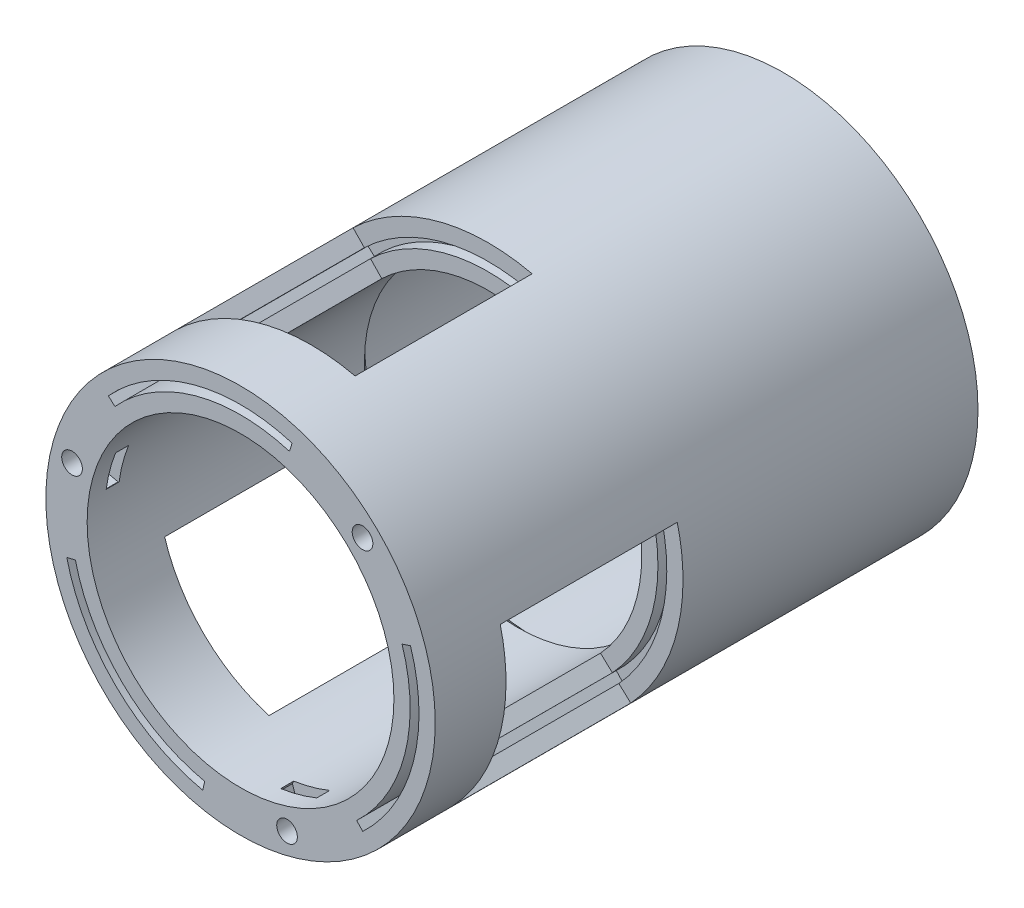
SolidWorks part; units mm, degrees
material "PEI"
ref_plane "Alzado" through (0, 0, 0) normal (0, 0, 1) x (1, 0, 0)
ref_plane "Planta" through (0, 0, 0) normal (0, 1, 0) x (1, 0, 0)
ref_plane "Vista lateral" through (0, 0, 0) normal (1, 0, 0) x (0, 0, -1)
sketch "Croquis1" plane through (0, 0, 0) normal (0, 0, 1) x (1, 0, 0)
  circle A0 centre (0, 0) radius 33
  circle A1 centre (0, 0) radius 29
  dimension "D1" = 66
  dimension "D2" = 4
extrude "Boss-Extrude1" add sketch "Croquis1" along normal blind 92
ref_axis "Eje1" through (0, 0, 92) along (0, 0, -1)
ref_plane "Plano corte lateral" through (0, 0, 0) normal (0.2419, -0.9703, 0) x (0, 0, -1)
sketch "Sketch8" plane through (0, 0, 0) normal (0, 0, -1) x (-1, 0, 0)
  arc A0 (-4, -28.7228) -> (4, -28.7228) centre (0, 0) ccw
  circle A1 centre (0, 0) radius 29 construction
  arc A2 (-4, -28.7228) -> (4, -28.7228) centre (0, -30.3008) cw
  arc A3 (-28.7228, 4) -> (-28.7228, -4) centre (0, 0) ccw
  arc A4 (-28.7228, 4) -> (-28.7228, -4) centre (-30.3008, 0) cw
  arc A5 (4, 28.7228) -> (-4, 28.7228) centre (0, 0) ccw
  arc A6 (4, 28.7228) -> (-4, 28.7228) centre (0, 30.3008) cw
  arc A7 (28.7228, -4) -> (28.7228, 4) centre (0, 0) ccw
  arc A8 (28.7228, -4) -> (28.7228, 4) centre (30.3008, 0) cw
  point P8 (0, -26.0008)
  point P20 (0, 0)
  dimension "D1" = 4.3
  dimension "D2" = 8
  dimension "D3" = 4
extrude "Boss-Extrude4" add sketch "Sketch8" against normal blind 15
sketch "Sketch9" plane through (0, 0, 0) normal (0, 0, -1) x (-1, 0, 0)
  circle A0 centre (0, -29) radius 1.75
  circle A1 centre (0, 0) radius 29 construction
  circle A2 centre (0, 0) radius 33 construction
  circle A3 centre (-29, 0) radius 1.75
  circle A4 centre (0, 29) radius 1.75
  circle A5 centre (29, 0) radius 1.75
  point P16 (0, 0)
  dimension "D1" = 4
  dimension "D2" = 3.5
  dimension "D3" = 4
extrude "Cut-Extrude3" cut sketch "Sketch9" against normal blind 14
ref_plane "Mid plane" through (0, 0, 46) normal (0, 0, 1) x (1, 0, 0)
ref_plane "Plano para USB y Switch" through (-23.3345, -23.3345, 0) normal (-0.7071, -0.7071, 0) x (0, 0, -1)
sketch "Sketch10" plane through (-23.3345, -23.3345, 0) normal (-0.7071, -0.7071, 0) x (0, 0, -1)
  line L0 (0, -33) -> (0, 33) construction
  line L1 (-10.5, 7.5) -> (-3.5, 7.5)
  line L2 (-10.5, 7.5) -> (-10.5, -7.5)
  line L3 (-10.5, -7.5) -> (-3.5, -7.5)
  line L4 (-3.5, 7.5) -> (-3.5, -7.5)
  line L5 (-10.5, 7.5) -> (-3.5, -7.5) construction
  line L6 (-10.5, -7.5) -> (-3.5, 7.5) construction
  line L8 (-45, 6.5) -> (-24, 6.5)
  line L9 (-45, 6.5) -> (-45, -6.5)
  line L10 (-45, -6.5) -> (-24, -6.5)
  line L11 (-24, 6.5) -> (-24, -6.5)
  line L12 (-45, 6.5) -> (-24, -6.5) construction
  line L13 (-45, -6.5) -> (-24, 6.5) construction
  point P0 (-7, 0)
  point P9 (-34.5, 0)
  dimension "D1" = 7
  dimension "D2" = 15
  dimension "D3" = 7
  dimension "D4" = 13
  dimension "D5" = 21
  dimension "D6" = 45
extrude "Corte USB y Switch" cut sketch "Sketch10" against normal blind 10
ref_plane "Plano tuercas superior" through (0, 0, 3) normal (0, 0, -1) x (-1, 0, 0)
sketch "Tuerca" plane through (0, 0, 3) normal (0, 0, -1) x (-1, 0, 0)
  line L30 (-29, -3.4064) -> (-25.5799, -3.4064)
  line L31 (-29, -3.4064) -> (-26.05, -1.7032) construction
  line L32 (-26.05, -1.7032) -> (-26.05, 1.7032) construction
  line L33 (-26.05, 1.7032) -> (-29, 3.4064) construction
  line L34 (-29, 3.4064) -> (-31.95, 1.7032)
  line L35 (-31.95, 1.7032) -> (-31.95, -1.7032)
  line L36 (-31.95, -1.7032) -> (-29, -3.4064)
  line L37 (-29, 3.4064) -> (-25.5799, 3.4064)
  circle A10 centre (-29, 0) radius 2.95 construction
  arc A12 (-25.5799, -3.4064) -> (-25.5799, 3.4064) centre (-28.2041, 0) ccw
  dimension "D4" = 5.9
extrude "Alojamiento tuerca" cut sketch "Tuerca" against normal blind 2.2 contours L30 A12 L37 L34 L35 L36 region at (27.8612, 0, 3)
pattern_circular "Alojamientos Tuercas Superior" count 4 over 360 about axis through (0, 0, 0) along (0, 0, 1) of "Alojamiento tuerca"
sketch "Sketch13" plane through (0, 0, 92) normal (0, 0, 1) x (1, 0, 0)
  circle A0 centre (0, 0) radius 29
  circle A1 centre (0, 0) radius 26
  circle A3 centre (0, 0) radius 29 construction
  circle A4 centre (0, 0) radius 33 construction
  dimension "D1" = 52
  dimension "D2" = 7
extrude "Grosor adicional" add sketch "Sketch13" against normal blind 47
sketch "Corte Revolucion" plane through (0, 0, 0) normal (0.2419, -0.9703, 0) x (0, 0, -1)
  line L0 (-80, 33) -> (-80, 25)
  line L2 (-80, 25) -> (-50, 25)
  line L4 (-50, 33) -> (-80, 33)
  line L5 (-97, 29) -> (-42, 29) construction
  line L6 (-92, 33) -> (-92, -33) construction
  line L14 (-50, 25) -> (-50, 33)
  dimension "D1" = 8
  dimension "D6" = 12
revolve "Cut-Revolve3" cut sketch "Corte Revolucion" angle 57 about axis through (0, 0, 92) along (0, 0, -1)
pattern_circular "CirPattern3" count 3 over 360 about axis through (0, 0, 0) along (0, 0, 1) of "Cut-Revolve3"
sketch "Croquis2" plane through (0, 0, 92) normal (0, 0, 1) x (1, 0, 0)
  line L0 (0, 0) -> (-22.4054, 20.3239) construction
  line L1 (0, 0) -> (8.7376, 28.9606) construction
  line L2 (0, 0) -> (-21.0134, 21.76) construction
  line L3 (0, 0) -> (6.8048, 29.4747) construction
  line L4 (8.7376, 28.9606) -> (8.3043, 27.5246)
  line L5 (-22.4054, 20.3239) -> (-21.2944, 19.3161)
  line L6 (20.7118, -22.0473) -> (19.6848, -20.954)
  line L7 (28.8037, 9.2417) -> (27.3754, 8.7834)
  line L8 (7.4234, 32.1542) -> (5.8487, 25.3336) construction
  line L9 (-22.9237, 23.7382) -> (-18.0611, 18.7028) construction
  line L10 (-29.4494, -6.9133) -> (-27.9891, -6.5705)
  line L11 (-6.3983, -29.5656) -> (-6.0811, -28.0995)
  circle A0 centre (0, 0) radius 28.75 construction
  circle A1 centre (0, 0) radius 30.25 construction
  arc A2 (28.8037, 9.2417) -> (20.7118, -22.0473) centre (0, 0) cw
  circle A3 centre (0, 0) radius 29.5 construction
  arc A4 (-22.4054, 20.3239) -> (8.7376, 28.9606) centre (0, 0) cw
  arc A5 (-21.2944, 19.3161) -> (8.3043, 27.5246) centre (0, 0) cw
  arc A6 (27.3754, 8.7834) -> (19.6848, -20.954) centre (0, 0) cw
  arc A7 (-6.3983, -29.5656) -> (-29.4494, -6.9133) centre (0, 0) cw
  arc A8 (-6.0811, -28.0995) -> (-27.9891, -6.5705) centre (0, 0) cw
  circle A13 centre (0, 0) radius 33 construction
  circle A14 centre (0, 0) radius 26 construction
  point P4 (-21.8499, 19.82)
  point P28 (0, 0)
  point P32 (0, 0)
  dimension "D1" = 1.5
  dimension "D2" = 7
  dimension "D6" = 3.5
  dimension "D3" = 2
  dimension "D4" = 2
  dimension "D5" = 3
extrude "Corte postizos" cut sketch "Croquis2" against normal offset from surface (44 mm away) 2 up to face at (-7.4059, 26.7047, 50) offset beyond the face yes
chamfer "Chamfer3" distance 3 angle 45 1 edges at (20.5061, 20.5061, 45)
sketch "Sketch14" plane through (0, 0, 92) normal (0, 0, 1) x (1, 0, 0)
  line L0 (8.3043, 27.5246) -> (0, 0) construction
  line L1 (0, 0) -> (27.3754, 8.7834) construction
  line L2 (0, 0) -> (20.6768, 21.0409) construction
  line L3 (28.8037, 9.2417) -> (27.3754, 8.7834) construction
  line L4 (8.7376, 28.9606) -> (8.3043, 27.5246) construction
  line L5 (0, 0) -> (7.8835, -28.4271) construction
  line L6 (0, 0) -> (-28.5604, 7.3862) construction
  arc A0 (28.0896, 9.0125) -> (8.5209, 28.2426) centre (0, 0) ccw construction
  circle A1 centre (20.6768, 21.0409) radius 1.75
  circle A2 centre (7.8835, -28.4271) radius 1.75
  arc A3 (-6.2397, -28.8326) -> (20.1983, -21.5006) centre (0, 0) ccw construction
  circle A4 centre (-28.5604, 7.3862) radius 1.75
  arc A5 (-21.8499, 19.82) -> (-28.7193, -6.7419) centre (0, 0) ccw construction
  point P21 (15.6241, 4.4801)
  point P25 (0, 0)
  dimension "D3" = 3.5
  dimension "D1" = 55.422
  dimension "D2" = 27.711
  dimension "D4" = 3
extrude "Cut-Extrude6" cut sketch "Sketch14" against normal blind 17
ref_plane "Plano tuercas inferior" through (0, 0, 89) normal (0, 0, 1) x (1, 0, 0)
sketch "Sketch15" plane through (0, 0, 89) normal (0, 0, 1) x (1, 0, 0)
  line L0 (18.1624, 23.3389) -> (15.8551, 20.8143)
  line L1 (18.1624, 23.3389) -> (17.4295, 20.0123) construction
  line L2 (17.4295, 20.0123) -> (19.9439, 17.7143) construction
  line L3 (19.9439, 17.7143) -> (23.1913, 18.7429) construction
  line L4 (23.1913, 18.7429) -> (23.9242, 22.0695)
  line L5 (23.9242, 22.0695) -> (21.4097, 24.3675)
  line L6 (21.4097, 24.3675) -> (18.1624, 23.3389)
  line L7 (23.1913, 18.7429) -> (20.884, 16.2183)
  line L8 (11.1309, -27.3985) -> (10.0982, -24.138)
  line L9 (4.6362, -29.4557) -> (7.1506, -31.7537)
  line L10 (7.1506, -31.7537) -> (10.398, -30.7251)
  line L11 (10.398, -30.7251) -> (11.1309, -27.3985)
  line L12 (4.6362, -29.4557) -> (3.6034, -26.1952)
  line L13 (11.1309, -27.3985) -> (8.6164, -25.1005) construction
  line L14 (8.6164, -25.1005) -> (5.3691, -26.1291) construction
  line L15 (5.3691, -26.1291) -> (4.6362, -29.4557) construction
  line L16 (-29.2933, 4.0596) -> (-25.9532, 3.3238)
  line L17 (-27.8274, 10.7128) -> (-31.0748, 9.6842)
  line L18 (-31.0748, 9.6842) -> (-31.8077, 6.3576)
  line L19 (-31.8077, 6.3576) -> (-29.2933, 4.0596)
  line L20 (-27.8274, 10.7128) -> (-24.4874, 9.9769)
  line L21 (-29.2933, 4.0596) -> (-26.0459, 5.0882) construction
  line L22 (-26.0459, 5.0882) -> (-25.313, 8.4148) construction
  line L23 (-25.313, 8.4148) -> (-27.8274, 10.7128) construction
  circle A0 centre (20.6768, 21.0409) radius 2.95 construction
  arc A1 (15.8551, 20.8143) -> (20.884, 16.2183) centre (20.1399, 20.4534) ccw
  arc A2 (10.0982, -24.138) -> (3.6034, -26.1952) centre (7.6432, -27.6684) ccw
  circle A3 centre (7.8835, -28.4271) radius 2.95 construction
  arc A5 (-25.9532, 3.3238) -> (-24.4874, 9.9769) centre (-27.7831, 7.215) ccw
  circle A6 centre (-28.5604, 7.3862) radius 2.95 construction
  point P11 (0, 0)
  point P12 (-28.5604, 7.3862)
  point P17 (20.6768, 21.0409)
  point P21 (0, 0)
  point P22 (0, 0)
  point P38 (0, 0)
  point P41 (0, 0)
  dimension "D1" = 5.9
  dimension "D2" = 240
  dimension "D3" = 240
  dimension "D4" = 210
  dimension "D5" = 240
  dimension "D6" = 3.4201
  dimension "D7" = 3
extrude "Tuercas inferior" cut sketch "Sketch15" against normal blind 2.2
equation "\"D6@Croquis2\"=\"D2@Croquis2\"/2"
equation "\"D2@Sketch14\"=\"D1@Sketch14\"/2"
equation "\"D3@Sketch15\"=\"D2@Sketch15\""
equation "\"D5@Sketch15\"=\"D3@Sketch15\""
